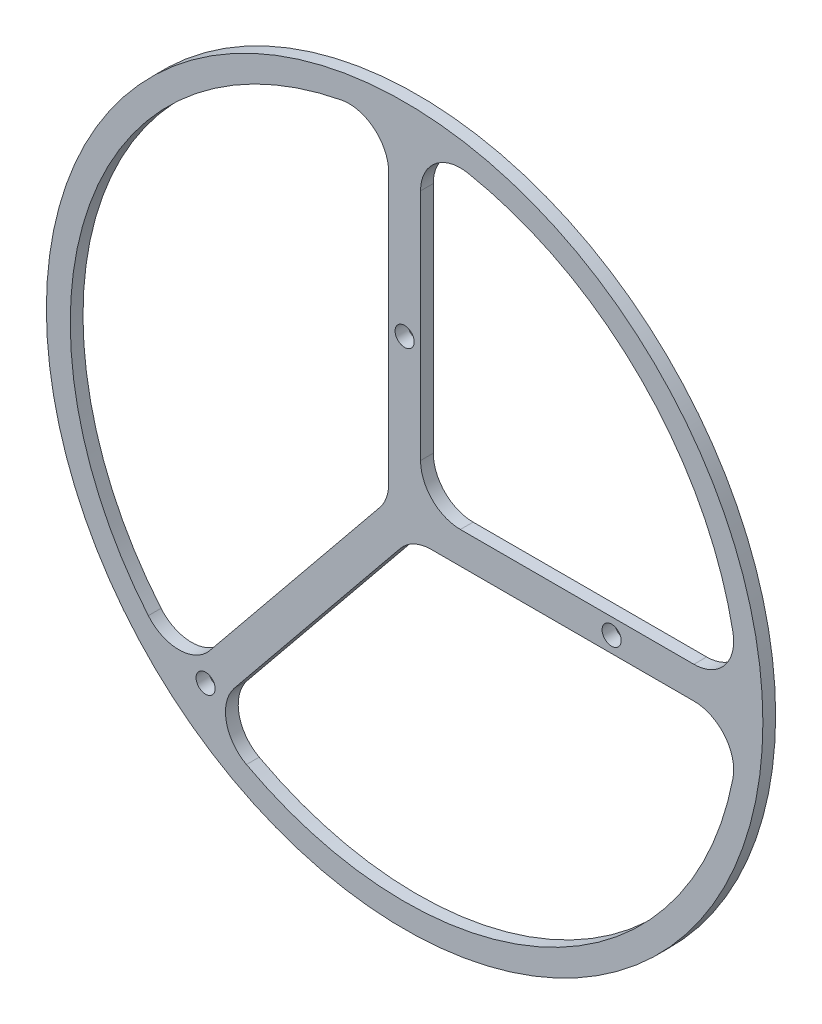
SolidWorks part; units mm, degrees
ref_plane "Front Plane" through (0, 0, 0) normal (1, 0, 0) x (0, 1, 0)
ref_plane "Top Plane" through (0, 0, 0) normal (0, 0, 1) x (0, 1, 0)
ref_plane "Right Plane" through (0, 0, 0) normal (0, 1, 0) x (-1, 0, 0)
sketch "Sketch5" plane through (0, 0, 0) normal (0, 0, 1) x (0, 1, 0)
  circle A0 centre (0, 0) radius 45
  dimension "D1" = 90
extrude "Boss-Extrude2" add sketch "Sketch5" along normal blind 1.6
sketch "Sketch2" plane through (0, 0, 0) normal (0, 0, 1) x (0, 1, 0)
  line L0 (19.5, 0) -> (0, 0) construction
  line L1 (0, 0) -> (0, -26) construction
  circle A0 centre (0, 0) radius 45
  point P0 (-39.5, -26)
  point P1 (0, -26)
  point P2 (19.5, 0)
  point P3 (-30.7215, 25)
  dimension "D6" = 90
  dimension "D1" = 39.5
  dimension "D2" = 59
  dimension "D3" = 26
  dimension "D4" = 51
  dimension "D5" = 51.75
hole_wizard "M2 Clearance Hole2" positions "Sketch2" profile "Sketch7" hole size "M2" standard "ANSI Metric"
sketch "Sketch7" plane through (-25, -30.7215, 0) normal (1, 0, 0) x (0, 1, 0)
  line L0 (0, 0) -> (0, 2.321)
  line L1 (0, 2.321) -> (1.2, 1.6)
  line L2 (1.2, 1.6) -> (1.2, 0)
  line L5 (1.2, 0) -> (0, 0)
  line L10 (0, 2.321) -> (-1.2, 1.6) construction
  line L11 (0, -6.35) -> (0, 107.95) construction
  dimension "Hole Dia." = 2.4
  dimension "Hole Depth" = 1.6
  dimension "Drill Angle" = 118
sketch "Sketch8" plane through (0, 0, 1.6) normal (0, 0, 1) x (1, 0, 0)
  line L0 (-25, -30.7215) -> (0, 0) construction
  line L1 (0, 0) -> (26, 0) construction
  line L2 (0, 0) -> (0, 19.5) construction
  line L3 (-25, -30.7215) -> (-26.5097, -32.5766) construction
  line L4 (26, 0) -> (42, 0) construction
  line L5 (0, 19.5) -> (0, 42) construction
  line L6 (-26.5513, -29.4591) -> (-28.0309, -31.2773)
  line L7 (-26.5513, -29.4591) -> (-2, 0.7109)
  line L8 (2, 2) -> (26, 2)
  line L9 (26, 2) -> (41.9524, 2)
  line L10 (-2, 0.7109) -> (-2, 19.5)
  line L11 (-2, 19.5) -> (-2, 41.9524)
  line L12 (-23.4487, -31.9838) -> (-24.9283, -33.8021)
  line L13 (-23.4487, -31.9838) -> (0.951, -2)
  line L14 (0.951, -2) -> (26, -2)
  line L15 (26, -2) -> (41.9524, -2)
  line L16 (2, 2) -> (2, 19.5)
  line L17 (2, 19.5) -> (2, 41.9524)
  line L19 (-26.5513, -29.4591) -> (-1.5513, 1.2624) construction
  line L20 (-2, 0) -> (-2, 19.5) construction
  line L21 (-23.4487, -31.9838) -> (1.5513, -1.2624) construction
  line L22 (0, -2) -> (26, -2) construction
  line L23 (2, 0) -> (2, 19.5) construction
  line L24 (0, 2) -> (26, 2) construction
  line L25 (-23.4487, -31.9838) -> (-24.9584, -33.839) construction
  line L26 (-26.5513, -29.4591) -> (-28.0609, -31.3143) construction
  line L27 (26, -2) -> (42, -2) construction
  line L28 (26, 2) -> (42, 2) construction
  line L29 (-2, 19.5) -> (-2, 42) construction
  line L30 (2, 19.5) -> (2, 42) construction
  circle A2 centre (0, 0) radius 42
  circle A3 centre (0, 0) radius 42
  circle A14 centre (-25, -30.7215) radius 1.2 construction
  circle A17 centre (26, 0) radius 1.2 construction
  circle A19 centre (0, 19.5) radius 1.2 construction
  circle A20 centre (-25, -30.7215) radius 1.2
  circle A22 centre (26, 0) radius 1.2
  circle A23 centre (0, 19.5) radius 1.2
  dimension "D1" = 3
  dimension "D5" = 2
  dimension "D6" = 2
extrude "Cut-Extrude1" cut sketch "Sketch8" against normal through all contours L12 A3 L15 L14 L13 | L11 A3 L6 L7 L10 | L9 A3 L17 L16 L8 region at (-21.2754, 7.5628, 1.6) region at (10.1219, -21.2867, 1.6) region at (18.7092, 18.7092, 1.6)
fillet "Fillet1" radius 5 9 edges at (-24.9283, -33.8021, 0.8) (-28.0309, -31.2773, 0.8) (-2, 0.7109, 0.8) (2, 2, 0.8) (0.951, -2, 0.8) (41.9524, -2, 0.8) (41.9524, 2, 0.8) (-2, 41.9524, 0.8) (2, 41.9524, 0.8)
